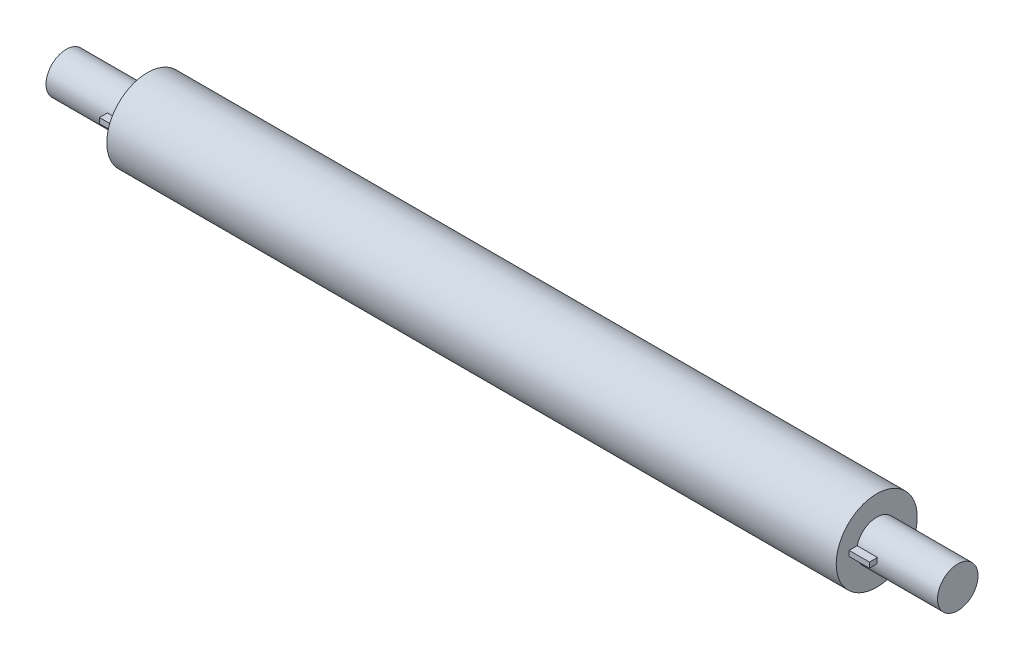
SolidWorks part; units mm, degrees
material "Nylon 101"
ref_plane "Front Plane" through (0, 0, 0) normal (0, 0, 1) x (1, 0, 0)
ref_plane "Top Plane" through (0, 0, 0) normal (0, 1, 0) x (1, 0, 0)
ref_plane "Right Plane" through (0, 0, 0) normal (1, 0, 0) x (0, 0, -1)
sketch "Sketch1" plane through (0, 0, 0) normal (0, 1, 0) x (1, 0, 0)
  line L0 (-110, 0) -> (110, 0)
  line L2 (-90, -5) -> (-90, -10)
  line L3 (-90, -10) -> (90, -10)
  line L4 (90, -5) -> (90, -10)
  line L7 (90, -5) -> (110, -5)
  line L8 (110, 0) -> (110, -5)
  line L11 (-90, -5) -> (-110, -5)
  line L12 (-110, 0) -> (-110, -5)
  dimension "D3" = 180
  dimension "D4" = 90
  dimension "D5" = 20
  dimension "D6" = 5
  dimension "D7" = 20
  dimension "D8" = 5
revolve "Revolve1" add sketch "Sketch1" angle 360 about L0
ref_axis "Axis1" through (90, 0, 0) along (-1, 0, 0)
sketch "Sketch2" plane through (90, 0, 0) normal (1, 0, 0) x (0, 0, -1)
  line L0 (-5, 0) -> (-6.8093, 0)
  line L1 (-6.8093, 0) -> (-6.8093, 1.3078)
  line L2 (-6.8093, 1.3078) -> (-4.8259, 1.3078)
  arc A0 (-4.8259, 1.3078) -> (-5, 0) centre (0, 0) ccw
extrude "Boss-Extrude1" add sketch "Sketch2" along normal blind 5
mirror "Mirror1" about plane through (0, 0, 0) normal (1, 0, 0) of "Boss-Extrude1"
